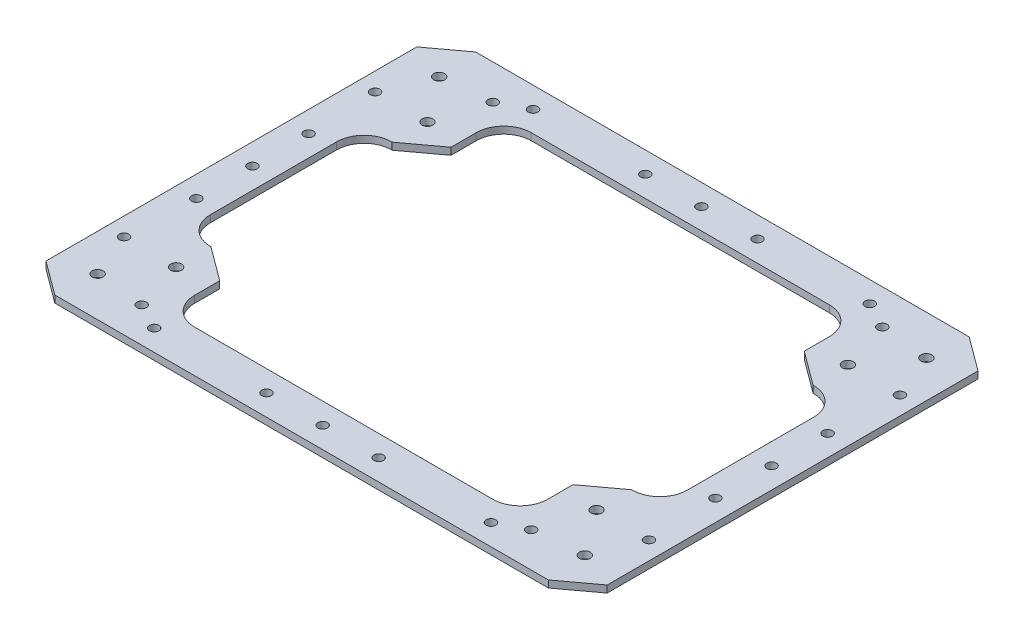
SolidWorks part; units mm, degrees
material "Thornel Mat VMA"
ref_plane "Front Plane" through (0, 0, 0) normal (0, 0, 1) x (1, 0, 0)
ref_plane "Top Plane" through (0, 0, 0) normal (0, 1, 0) x (1, 0, 0)
ref_plane "Right Plane" through (0, 0, 0) normal (1, 0, 0) x (0, 0, -1)
sketch "Sketch1" plane through (0, 0, 0) normal (0, 1, 0) x (1, 0, 0)
  line L0 (-127, 83.9186) -> (-111.6865, 95.25)
  line L1 (-127, -95.25) -> (127, -95.25)
  line L2 (-127, -95.25) -> (-127, 95.25)
  line L3 (-127, 95.25) -> (127, 95.25)
  line L4 (127, -95.25) -> (127, 95.25)
  line L5 (-107.95, 28.565) -> (-107.95, -28.565)
  line L7 (67.4905, 76.2) -> (-67.4905, 76.2)
  line L8 (-95.504, 41.011) -> (-95.25, 41.011)
  line L9 (-67.4905, -76.2) -> (67.4905, -76.2)
  line L10 (-127, 95.25) -> (127, -95.25) construction
  line L12 (127, 83.9186) -> (111.6865, 95.25)
  line L14 (79.9365, 52.3423) -> (79.9365, 63.754)
  line L15 (95.25, 41.011) -> (79.9365, 52.3423)
  line L16 (95.504, 41.011) -> (95.25, 41.011)
  line L17 (107.95, 28.565) -> (107.95, -28.565)
  line L18 (127, -83.9186) -> (111.6865, -95.25)
  line L19 (95.504, -41.011) -> (95.25, -41.011)
  line L20 (95.25, -41.011) -> (79.9365, -52.3423)
  line L21 (79.9365, -52.3423) -> (79.9365, -63.754)
  line L22 (127, 0) -> (-127, 0) construction
  line L23 (0, -13.6985) -> (0, 95.25) construction
  line L25 (-107.95, 28.565) -> (-95.504, 28.565) construction
  line L26 (-79.9365, -52.3423) -> (-79.9365, -63.754)
  line L27 (-95.25, 41.011) -> (-127, 83.9186) construction
  line L28 (-95.25, 41.011) -> (-79.9365, 52.3423)
  line L29 (-79.9365, 52.3423) -> (-79.9365, 63.754)
  line L31 (-95.25, -41.011) -> (-79.9365, -52.3423)
  line L32 (-95.504, -41.011) -> (-95.25, -41.011)
  line L33 (-127, -83.9186) -> (-111.6865, -95.25)
  line L34 (-79.9365, 52.3423) -> (-111.6865, 95.25) construction
  arc A0 (-79.9365, 63.754) -> (-67.4905, 76.2) centre (-67.4905, 63.754) cw
  arc A1 (79.9365, 63.754) -> (67.4905, 76.2) centre (67.4905, 63.754) ccw
  arc A2 (79.9365, -63.754) -> (67.4905, -76.2) centre (67.4905, -63.754) cw
  arc A3 (-67.4905, -76.2) -> (-79.9365, -63.754) centre (-67.4905, -63.754) cw
  arc A4 (-95.504, -41.011) -> (-107.95, -28.565) centre (-95.504, -28.565) cw
  arc A5 (-107.95, 28.565) -> (-95.504, 41.011) centre (-95.504, 28.565) cw
  arc A6 (95.504, 41.011) -> (107.95, 28.565) centre (95.504, 28.565) cw
  arc A7 (95.504, -41.011) -> (107.95, -28.565) centre (95.504, -28.565) ccw
  point P0 (0, 0)
  point P1 (0, 0)
  point P7 (0, -95.25)
  point P14 (0, 0)
  point P22 (0, 76.2)
  point P25 (0, 0)
  point P29 (65.7602, -76.2)
  point P33 (107.95, 0)
  point P34 (65.4936, 76.2)
  point P35 (79.9365, 52.3423)
  point P41 (0, 0)
  point P44 (-107.95, 0)
  point P45 (-38.1, 0)
  point P46 (-31.75, 0)
  point P47 (67.4905, 76.2)
  dimension "D10" = 12.446
  dimension "D1" = 190.5
  dimension "D2" = 254
  dimension "D3" = 19.05
  dimension "D4" = 19.05
  dimension "D9" = 76.2
  dimension "D5" = 53.5
  dimension "D6" = 19.05
  dimension "D8" = 79.9365
extrude "Boss-Extrude1" add sketch "Sketch1" along normal blind 3.175 contours L2 L1 L4 L3 L8 region at (-117.4547, 0, -87.0321)
sketch "Sketch2" plane through (0, 3.175, 0) normal (0, 1, 0) x (1, 0, 0)
  line L0 (-87.5933, 46.6767) -> (-119.3433, 89.5843) construction
  line L1 (-95.25, 41.011) -> (-79.9365, 52.3423) construction
  line L2 (-127, 83.9186) -> (-111.6865, 95.25) construction
  line L3 (0, 0) -> (0, 95.25) construction
  line L4 (-111.6865, 95.25) -> (111.6865, 95.25) construction
  line L5 (0, 0) -> (-127, 0) construction
  line L6 (-127, -83.9186) -> (-127, 83.9186) construction
  line L7 (-103.4683, 68.1305) -> (-88.1548, 79.4619) construction
  circle A0 centre (-95.1475, 56.8856) radius 2.4638
  circle A1 centre (-110.256, 77.3036) radius 2.4638
  circle A2 centre (110.256, 77.3036) radius 2.4638
  circle A3 centre (95.1475, 56.8856) radius 2.4638
  circle A4 centre (110.256, -77.3036) radius 2.4638
  circle A5 centre (95.1475, -56.8856) radius 2.4638
  circle A6 centre (-110.256, -77.3036) radius 2.4638
  circle A7 centre (-95.1475, -56.8856) radius 2.4638
  circle A8 centre (-88.1548, 79.4619) radius 2.159
  circle A9 centre (-118.7817, 56.7991) radius 2.159
  circle A10 centre (118.7817, 56.7991) radius 2.159
  circle A11 centre (88.1548, 79.4619) radius 2.159
  circle A12 centre (118.7817, -56.7991) radius 2.159
  circle A13 centre (88.1548, -79.4619) radius 2.159
  circle A14 centre (-88.1548, -79.4619) radius 2.159
  circle A15 centre (-118.7817, -56.7991) radius 2.159
  dimension "D2" = 4.9276
  dimension "D3" = 4.9276
  dimension "D5" = 4.318
  dimension "D1" = 25.4
  dimension "D4" = 12.7
  dimension "D6" = 19.05
extrude "Cut-Extrude1" cut sketch "Sketch2" against normal through all
sketch "Sketch3" plane through (0, 3.175, 0) normal (0, 1, 0) x (1, 0, 0)
  line L0 (-79.9365, 76.2) -> (-79.9365, 95.25) construction
  line L1 (-111.6865, 95.25) -> (111.6865, 95.25) construction
  line L2 (-79.9365, 85.725) -> (79.9365, 85.725) construction
  line L3 (79.9365, 76.2) -> (79.9365, 95.25) construction
  line L4 (0, 0) -> (76.2, 0) construction
  line L5 (-107.95, -41.011) -> (-127, -41.011) construction
  line L6 (-127, -83.9186) -> (-127, 83.9186) construction
  line L7 (-107.95, 41.011) -> (-127, 41.011) construction
  line L8 (-117.475, 41.011) -> (-117.475, -41.011) construction
  line L9 (0, 0) -> (0, 36.2879) construction
  line L11 (127, -83.9186) -> (127, 83.9186) construction
  circle A0 centre (-76.2, 85.725) radius 2.159
  circle A1 centre (-25.4, 85.725) radius 2.159
  circle A2 centre (25.4, 85.725) radius 2.159
  circle A3 centre (76.2, 85.725) radius 2.159
  circle A4 centre (76.2, -85.725) radius 2.159
  circle A5 centre (25.4, -85.725) radius 2.159
  circle A6 centre (-25.4, -85.725) radius 2.159
  circle A7 centre (-76.2, -85.725) radius 2.159
  circle A8 centre (-117.475, -25.4) radius 2.159
  circle A9 centre (-117.475, 25.4) radius 2.159
  circle A10 centre (117.475, 25.4) radius 2.159
  circle A11 centre (117.475, -25.4) radius 2.159
  circle A12 centre (0, 85.725) radius 2.159
  circle A13 centre (0, -85.725) radius 2.159
  circle A14 centre (-117.475, 0) radius 2.159
  circle A15 centre (117.475, 0) radius 2.159
  point P12 (0, 85.725)
  point P40 (-117.475, 0)
  dimension "D1" = 4.318
  dimension "D2" = 76.2
  dimension "D4" = 4.318
  dimension "D5" = 25.4
  dimension "D7" = 85.725
  dimension "D8" = 127
  dimension "D9" = 127
  dimension "D3" = 4
  dimension "D6" = 2
extrude "Cut-Extrude2" cut sketch "Sketch3" against normal through all
sketch "Sketch4" plane through (0, 3.175, 0) normal (0, 1, 0) x (1, 0, 0)
  line L0 (-95.1475, -56.8856) -> (-110.256, -74.8398) construction
